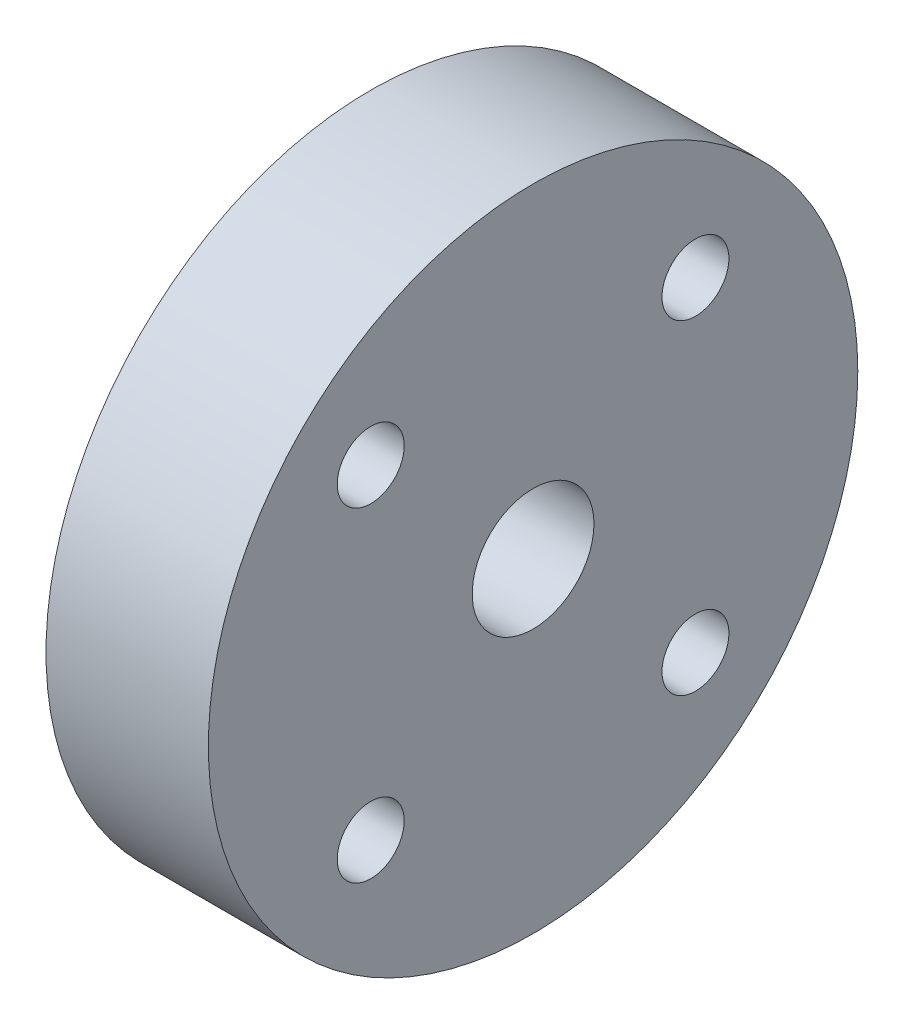
SolidWorks part; units mm, degrees
ref_plane "Front Plane" through (0, 0, 0) normal (0, 0, 1) x (1, 0, 0)
ref_plane "Top Plane" through (0, 0, 0) normal (0, 1, 0) x (1, 0, 0)
ref_plane "Right Plane" through (0, 0, 0) normal (1, 0, 0) x (0, 0, -1)
sketch "SK_Body" plane through (0, 0, 0) normal (1, 0, 0) x (0, 0, -1)
  circle A0 centre (0, 0) radius 16
  dimension "D1" = 32
extrude "EX_Body" add sketch "SK_Body" along normal blind 8
sketch "SK_Bore" plane through (0, 0, 0) normal (1, 0, 0) x (0, 0, -1)
  circle A0 centre (0, 0) radius 3
  dimension "D1" = 6
extrude "CUT_Bore" cut sketch "SK_Bore" along normal blind 8
ref_plane "PL_Yp8" through (8, 0, 0) normal (1, 0, 0) x (0, 0, -1)
sketch "SK_Pattern16_4xM4" plane through (8, 0, 0) normal (1, 0, 0) x (0, 0, -1)
  circle A0 centre (-8, 8) radius 1.65
  circle A1 centre (-8, -8) radius 1.65
  circle A2 centre (8, 8) radius 1.65
  circle A3 centre (8, -8) radius 1.65
  dimension "D3" = 3.3
  dimension "D6" = 3.3
  dimension "D9" = 3.3
  dimension "D12" = 3.3
  dimension "D1" = 8
  dimension "D2" = 8
  dimension "D4" = 8
  dimension "D5" = 8
  dimension "D7" = 8
  dimension "D8" = 8
  dimension "D10" = 8
  dimension "D11" = 8
extrude "CUT_Pattern16_4xM4" cut sketch "SK_Pattern16_4xM4" against normal blind 6
ref_axis "AX_X" through (0, 0, -17.6) along (0, 0, 1)
ref_axis "AX_Y" through (8.4, 0, 0) along (-1, 0, 0)
ref_axis "AX_Z" through (0, 17.6, 0) along (0, -1, 0)
sketch "SK_F_IF_WheelFace" plane through (0, 0, 0) normal (0, 1, 0) x (1, 0, 0)
  point P0 (8, 0)
  dimension "D1" = 8
